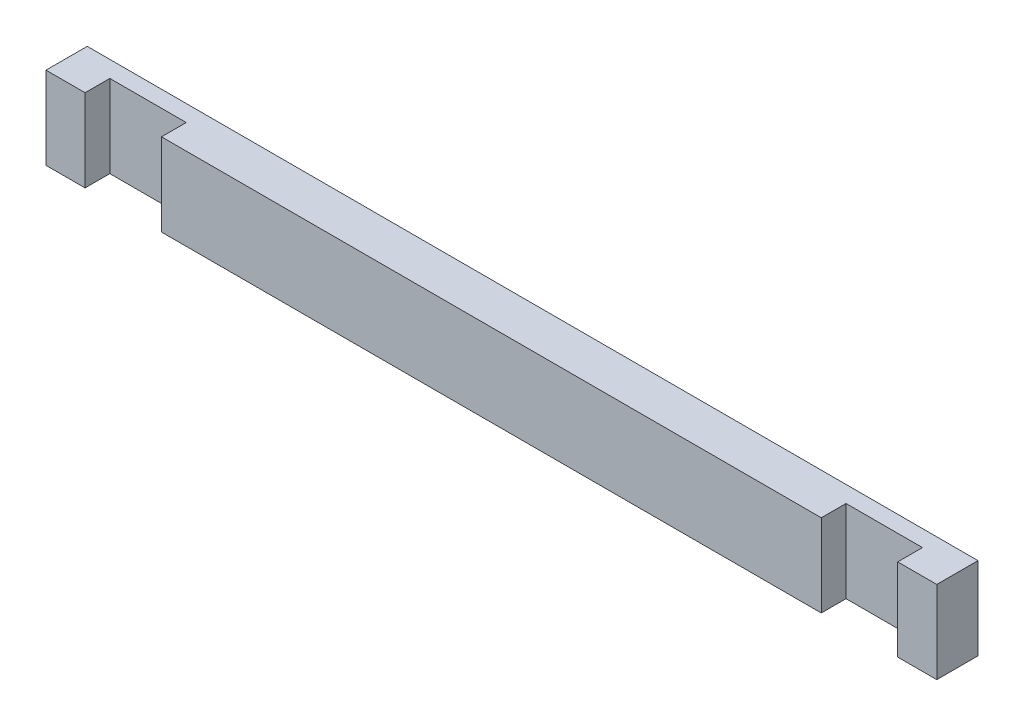
SolidWorks part; units mm, degrees
ref_plane "Спереди" through (0, 0, 0) normal (0, 0, 1) x (1, 0, 0)
ref_plane "Сверху" through (0, 0, 0) normal (0, 1, 0) x (1, 0, 0)
ref_plane "Справа" through (0, 0, 0) normal (1, 0, 0) x (0, 0, -1)
sketch "Эскиз1" plane through (0, 0, 0) normal (0, 1, 0) x (1, 0, 0)
  line L0 (200, 0) -> (-200, 0)
  line L5 (-200, 0) -> (-200, 15)
  line L6 (-200, 15) -> (-246.3169, 15)
  line L7 (-246.3169, 15) -> (-246.3169, 0)
  line L8 (-246.3169, 0) -> (-270, 0)
  line L9 (-270, 0) -> (-270, 25)
  line L10 (-270, 25) -> (270, 25)
  line L11 (0, 22.2095) -> (0, -15.1214) construction
  line L12 (270, 0) -> (270, 25)
  line L13 (246.3169, 0) -> (270, 0)
  line L14 (246.3169, 15) -> (246.3169, 0)
  line L15 (200, 15) -> (246.3169, 15)
  line L16 (200, 0) -> (200, 15)
  point P0 (0, 0)
  point P3 (0, 0)
  point P16 (0, 25)
  point P21 (0, 0)
extrude "Бобышка-Вытянуть1" add sketch "Эскиз1" along normal blind 50
